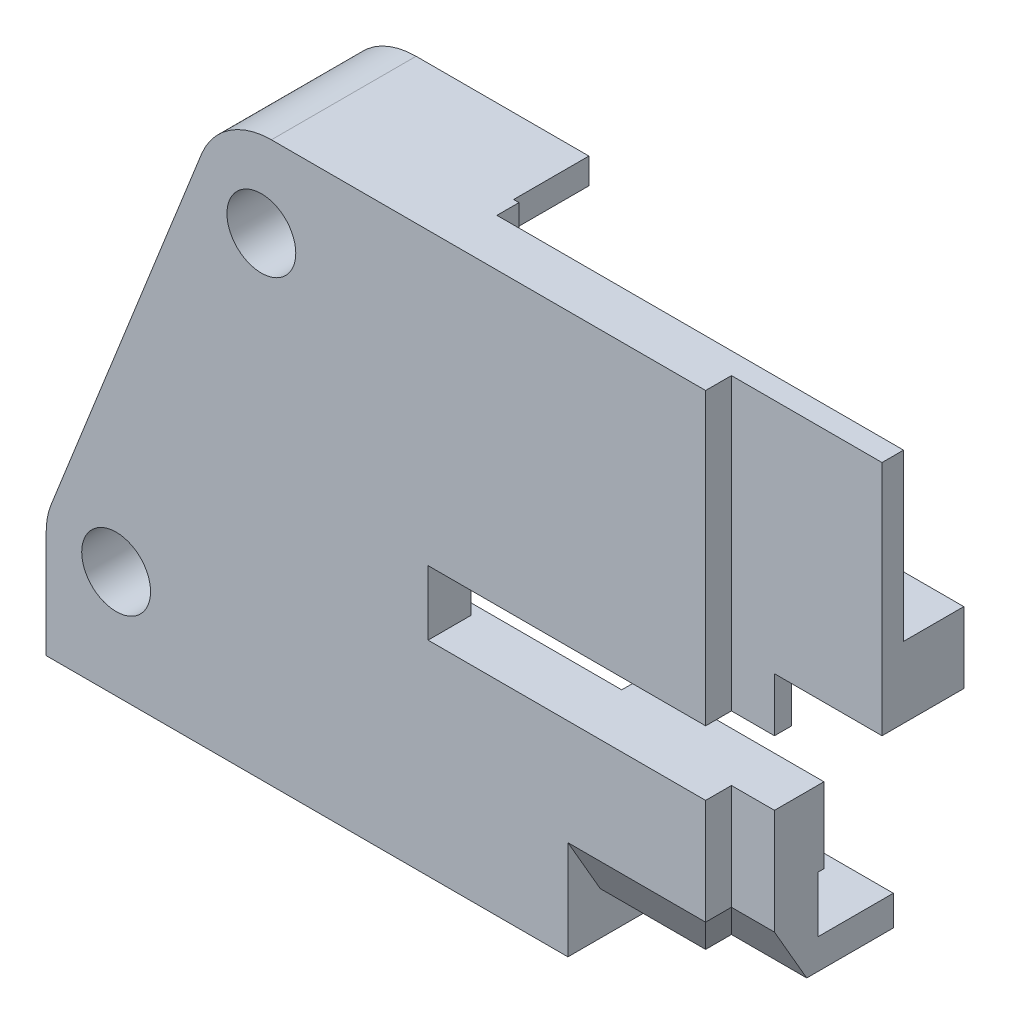
SolidWorks part; units mm, degrees
ref_plane "前视基准面" through (0, 0, 0) normal (0, 0, 1) x (1, 0, 0)
ref_plane "上视基准面" through (0, 0, 0) normal (0, 1, 0) x (1, 0, 0)
ref_plane "右视基准面" through (0, 0, 0) normal (1, 0, 0) x (0, 0, -1)
other "Configuration Table"
sketch "草图1" plane through (0, 0, 0) normal (0, 0, 1) x (1, 0, 0)
  line L1 (-4, 6.5) -> (6, 6.5)
  line L2 (-4, 6.5) -> (-4, -5)
  line L3 (-4, -5) -> (6, -5)
  line L4 (6, 6.5) -> (6, -5)
  circle A0 centre (0, 0) radius 1.6
  dimension "D1" = 3.2
  dimension "D2" = 5
  dimension "D3" = 4
  dimension "D4" = 11.5
  dimension "D5" = 10
extrude "凸台-拉伸1" add sketch "草图1" along normal blind 3
sketch "草图2" plane through (0, 0, 3) normal (0, 0, 1) x (1, 0, 0)
  line L1 (6, -5) -> (21, -5)
  line L2 (6, -5) -> (6, 1)
  line L3 (6, 1) -> (21, 1)
  line L4 (21, -5) -> (21, 1)
  dimension "D1" = 6
  dimension "D2" = 15
extrude "凸台-拉伸2" add sketch "草图2" against normal blind 5
fillet "圆角1" radius 1 1 edges at (-4, 0.75, 0)
sketch "草图3" plane through (0, 1, 0) normal (0, 1, 0) x (1, 0, 0)
  line L0 (21, -3) -> (6, -3) construction
  line L1 (6, 2) -> (11, 2)
  line L2 (6, 2) -> (6, -3)
  line L3 (6, -3) -> (11, -3)
  line L4 (11, 2) -> (11, -3)
  dimension "D1" = 5
extrude "凸台-拉伸3" add sketch "草图3" along normal blind 2
sketch "草图4" plane through (0, 3, 0) normal (0, 1, 0) x (1, 0, 0)
  line L0 (6, 2) -> (6, 0) construction
  line L1 (6, 0) -> (11, 0)
  line L2 (6, 0) -> (6, -3)
  line L3 (6, -3) -> (11, -3)
  line L4 (11, 0) -> (11, -3)
  dimension "D1" = 3
extrude "凸台-拉伸4" add sketch "草图4" along normal blind 19.5
sketch "草图5" plane through (0, 0, 0) normal (0, 0, -1) x (-1, 0, 0)
  line L0 (-6, 22.5) -> (-6, 6.5) construction
  line L1 (-6, 10) -> (-11, 10)
  line L2 (-6, 10) -> (-6, 13.5)
  line L3 (-6, 13.5) -> (-11, 13.5)
  line L4 (-11, 10) -> (-11, 13.5)
  line L5 (-11, 22.5) -> (-11, 3) construction
  line L6 (-11, 3) -> (-6, 3) construction
  line L7 (-11, 3) -> (-6, 3) construction
  dimension "D1" = 7
  dimension "D2" = 10.5
extrude "凸台-拉伸5" add sketch "草图5" along normal blind 3
sketch "草图6" plane through (6, 0, 0) normal (-1, 0, 0) x (0, 0, 1)
  line L1 (3, 22.5) -> (0, 22.5)
  line L2 (3, 22.5) -> (3, 14)
  line L3 (3, 14) -> (0, 14)
  line L4 (0, 22.5) -> (0, 14)
  line L5 (0, 22.5) -> (0, 13.5) construction
  dimension "D1" = 8.5
extrude "凸台-拉伸6" add sketch "草图6" along normal blind 3
sketch "草图7" plane through (0, 0, 0) normal (0, 0, -1) x (-1, 0, 0)
  line L6 (-11, 13.5) -> (-6, 13.5)
  line L7 (-6, 13.5) -> (-6, 14)
  line L8 (-6, 14) -> (-3, 14)
  line L9 (-3, 14) -> (-3, 22.5)
  line L10 (-3, 22.5) -> (-11, 22.5)
  line L11 (-11, 22.5) -> (-11, 13.5)
  line L12 (-11, 13.5) -> (-6, 13.5)
  line L13 (-6, 13.5) -> (-6, 14)
  line L14 (-6, 14) -> (-3, 14)
  line L15 (-3, 14) -> (-3, 22.5)
  line L16 (-3, 22.5) -> (-11, 22.5)
  line L17 (-11, 22.5) -> (-11, 13.5)
  dimension "D1" = 0
extrude "凸台-拉伸7" add sketch "草图7" along normal blind 1
sketch "草图8" plane through (0, 0, 3) normal (0, 0, 1) x (1, 0, 0)
  line L0 (21, 1) -> (11, 1) construction
  line L1 (11, 22.5) -> (14.5, 22.5)
  line L2 (11, 22.5) -> (11, 1)
  line L3 (11, 1) -> (14.5, 1)
  line L4 (14.5, 22.5) -> (14.5, 1)
  dimension "D1" = 3.5
extrude "凸台-拉伸8" add sketch "草图8" against normal blind 1
sketch "草图9" plane through (11, 0, 0) normal (1, 0, 0) x (0, 0, -1)
  line L0 (1, 22.5) -> (1, 13.5) construction
  line L1 (-2, 22.5) -> (1, 22.5)
  line L2 (-2, 22.5) -> (-2, 14.5)
  line L3 (-2, 14.5) -> (1, 14.5)
  line L4 (1, 22.5) -> (1, 14.5)
  dimension "D1" = 8
extrude "凸台-拉伸9" add sketch "草图9" along normal up to surface (3.5 mm away) up to face at (14.5, 11.75, 2.5)
sketch "草图10" plane through (11, 0, 0) normal (1, 0, 0) x (0, 0, -1)
  line L1 (-0.5, 4.5) -> (-3, 4.5)
  line L2 (-0.5, 4.5) -> (-0.5, 1)
  line L3 (-0.5, 1) -> (-3, 1)
  line L4 (-3, 4.5) -> (-3, 1)
  line L5 (-3, -5) -> (-3, 1) construction
  line L6 (2, 1) -> (-3, 1) construction
  line L7 (0, 10) -> (0, 3) construction
  dimension "D1" = 3.5
  dimension "D2" = 0.5
extrude "凸台-拉伸10" add sketch "草图10" along normal up to surface (10 mm away) up to face at (21, -2, 0.5)
sketch "草图11" plane through (11, 0, 0) normal (1, 0, 0) x (0, 0, -1)
  line L0 (-2, 14.5) -> (1, 14.5) construction
  line L1 (0, 14.5) -> (-3, 14.5)
  line L2 (0, 14.5) -> (0, 10.5)
  line L3 (0, 10.5) -> (-3, 10.5)
  line L4 (-3, 14.5) -> (-3, 10.5)
  line L5 (-3, 4.5) -> (-3, 22.5) construction
  dimension "D1" = 4
  dimension "D2" = 3
extrude "凸台-拉伸11" add sketch "草图11" along normal up to surface (10 mm away) up to face at (21, 0.1667, 0.5)
sketch "草图12" plane through (21, 0, 0) normal (1, 0, 0) x (0, 0, -1)
  line L1 (0, 14.5) -> (-1.5, 14.5)
  line L2 (0, 14.5) -> (0, 13.3)
  line L3 (0, 13.3) -> (-1.5, 13.3)
  line L4 (-1.5, 14.5) -> (-1.5, 13.3)
  dimension "D1" = 1.5
  dimension "D2" = 1.2
extrude "切除-拉伸1" cut sketch "草图12" against normal blind 2
sketch "草图13" plane through (14.5, 0, 0) normal (1, 0, 0) x (0, 0, -1)
  line L0 (-2, 10.5) -> (-2, 4.5) construction
  line L1 (-3, 10.5) -> (-2, 10.5)
  line L2 (-3, 10.5) -> (-3, 8)
  line L3 (-3, 8) -> (-2, 8)
  line L4 (-2, 10.5) -> (-2, 8)
  dimension "D1" = 2.5
extrude "凸台-拉伸12" add sketch "草图13" along normal up to surface (6.5 mm away) up to face at (21, 12.7667, 1.5)
sketch "草图14" plane through (14.5, 0, 0) normal (1, 0, 0) x (0, 0, -1)
  line L0 (1, 22.5) -> (-3, 22.5) construction
  line L1 (-1.8, 22.5) -> (-3, 22.5)
  line L2 (-1.8, 22.5) -> (-1.8, 14.5)
  line L3 (-1.8, 14.5) -> (-3, 14.5)
  line L4 (-3, 22.5) -> (-3, 14.5)
  dimension "D1" = 1.2
extrude "凸台-拉伸13" add sketch "草图14" along normal up to surface (6.5 mm away) up to face at (21, 11.575, 1.625)
sketch "草图15" plane through (0, 0, 1.8) normal (0, 0, -1) x (-1, 0, 0)
  line L1 (-14.5, 14.5) -> (-18.5, 14.5)
  line L2 (-14.5, 14.5) -> (-14.5, 18.5)
  line L3 (-14.5, 18.5) -> (-18.5, 18.5)
  line L4 (-18.5, 14.5) -> (-18.5, 18.5)
  dimension "D1" = 4
extrude "凸台-拉伸14" add sketch "草图15" along normal up to surface (2.8 mm away)
fillet "圆角2" radius 1 1 edges at (14.5, 18.5, 0.4)
sketch "草图16" plane through (0, 0, 3) normal (0, 0, 1) x (1, 0, 0)
  line L0 (3, 14) -> (3, 22.5) construction
  line L1 (3, 22.5) -> (21, 22.5) construction
  circle A0 centre (6.75, 17) radius 1.6
  dimension "D1" = 3.75
  dimension "D2" = 5.5
  dimension "D3" = 3.2
extrude "切除-拉伸2" cut sketch "草图16" against normal up to next
sketch "草图17" plane through (0, -5, 0) normal (0, -1, 0) x (1, 0, 0)
  line L1 (6, -2) -> (21, -2)
  line L2 (6, -2) -> (6, 3)
  line L3 (6, 3) -> (21, 3)
  line L4 (21, -2) -> (21, 3)
extrude "凸台-拉伸15" add sketch "草图17" along normal blind 2
sketch "草图18" plane through (21, 0, 0) normal (1, 0, 0) x (0, 0, -1)
  line L10 (0, 13.3) -> (-1.5, 13.3)
  line L11 (0, 13.3) -> (-1.5, 13.3)
  line L12 (-1.5, 14.5) -> (-1.8, 14.5)
  line L13 (-1.8, 14.5) -> (-1.8, 22.5)
  line L14 (-1.8, 22.5) -> (-3, 22.5)
  line L15 (-3, 22.5) -> (-3, 8)
  line L16 (-3, 8) -> (-2, 8)
  line L17 (-2, 8) -> (-2, 10.5)
  line L18 (-2, 10.5) -> (0, 10.5)
  line L19 (0, 10.5) -> (0, 13.3)
  line L22 (-1.5, 14.5) -> (-1.8, 14.5)
  line L23 (-1.8, 14.5) -> (-1.8, 22.5)
  line L24 (-1.8, 22.5) -> (-3, 22.5)
  line L25 (-3, 22.5) -> (-3, 8)
  line L26 (-3, 8) -> (-2, 8)
  line L27 (-2, 8) -> (-2, 10.5)
  line L28 (-2, 10.5) -> (0, 10.5)
  line L29 (0, 10.5) -> (0, 13.3)
  line L30 (-1.5, 13.3) -> (-1.5, 14.5)
  line L31 (-1.5, 13.3) -> (-1.5, 14.5)
  dimension "D1" = 0
extrude "凸台-拉伸16" add sketch "草图18" along normal blind 5.5
sketch "草图19" plane through (0, 0, 0) normal (0, 0, -1) x (-1, 0, 0)
  line L0 (-19, 13.3) -> (-26.5, 13.3) construction
  line L1 (-24.5, 13.3) -> (-26.5, 13.3)
  line L2 (-24.5, 13.3) -> (-24.5, 10.5)
  line L3 (-24.5, 10.5) -> (-26.5, 10.5)
  line L4 (-26.5, 13.3) -> (-26.5, 10.5)
  dimension "D1" = 2
extrude "凸台-拉伸17" add sketch "草图19" along normal blind 2
sketch "草图20" plane through (21, 0, 0) normal (1, 0, 0) x (0, 0, -1)
  line L1 (0.5, -3) -> (-3, -3)
  line L2 (0.5, 1) -> (0.5, 4.5)
  line L3 (0.5, 4.5) -> (-3, 4.5)
  line L4 (-3, -3) -> (-3, 4.5)
  line L5 (2, -7) -> (2, 1) construction
  line L7 (2, 1) -> (0.5, 1)
  line L8 (2, 1) -> (2, -3)
  line L9 (2, -3) -> (0.5, -3)
  dimension "D1" = 1.5
  dimension "D2" = 7.5
extrude "凸台-拉伸18" add sketch "草图20" along normal up to surface (5.5 mm away) up to face at (26.5, 13.76, 1.26)
sketch "草图21" plane through (26.5, 0, 0) normal (1, 0, 0) x (0, 0, -1)
  line L6 (-3, -3) -> (2, -3)
  line L7 (2, -3) -> (2, 1)
  line L8 (2, 1) -> (0.5, 1)
  line L9 (0.5, 1) -> (0.5, 4.5)
  line L10 (0.5, 4.5) -> (-3, 4.5)
  line L11 (-3, 4.5) -> (-3, -3)
  line L12 (-3, -3) -> (2, -3)
  line L13 (2, -3) -> (2, 1)
  line L14 (2, 1) -> (0.5, 1)
  line L15 (0.5, 1) -> (0.5, 4.5)
  line L16 (0.5, 4.5) -> (-3, 4.5)
  line L17 (-3, 4.5) -> (-3, -3)
  line L22 (-2, 10.5) -> (2, 10.5)
  line L23 (2, 10.5) -> (2, 13.3)
  line L24 (2, 13.3) -> (-1.5, 13.3)
  line L26 (-1.5, 14.5) -> (-1.8, 14.5)
  line L27 (-1.8, 14.5) -> (-1.8, 22.5)
  line L28 (-1.8, 22.5) -> (-3, 22.5)
  line L29 (-3, 22.5) -> (-3, 8)
  line L30 (-3, 8) -> (-2, 8)
  line L31 (-2, 8) -> (-2, 10.5)
  line L32 (-2, 10.5) -> (2, 10.5)
  line L33 (2, 10.5) -> (2, 13.3)
  line L36 (-1.5, 14.5) -> (-1.8, 14.5)
  line L37 (-1.8, 14.5) -> (-1.8, 22.5)
  line L38 (-1.8, 22.5) -> (-3, 22.5)
  line L39 (-3, 22.5) -> (-3, 8)
  line L40 (-3, 8) -> (-2, 8)
  line L41 (-2, 8) -> (-2, 10.5)
  line L42 (2, 13.3) -> (-1.5, 13.3)
  line L44 (-1.5, 13.3) -> (-1.5, 14.5)
  line L45 (-1.5, 13.3) -> (-1.5, 14.5)
  dimension "D1" = 0
  dimension "D2" = 0
extrude "凸台-拉伸19" add sketch "草图21" along normal blind 2.9
sketch "草图22" plane through (0, 0, 2) normal (0, 0, -1) x (-1, 0, 0)
  line L6 (-11, 10.5) -> (-29.4, 10.5)
  line L7 (-29.4, 10.5) -> (-29.4, 8)
  line L8 (-29.4, 8) -> (-14.5, 8)
  line L9 (-14.5, 8) -> (-14.5, 4.5)
  line L10 (-14.5, 4.5) -> (-11, 4.5)
  line L11 (-11, 4.5) -> (-11, 10.5)
  line L12 (-11, 10.5) -> (-29.4, 10.5)
  line L13 (-29.4, 10.5) -> (-29.4, 8)
  line L14 (-29.4, 8) -> (-14.5, 8)
  line L15 (-14.5, 8) -> (-14.5, 4.5)
  line L16 (-14.5, 4.5) -> (-11, 4.5)
  line L17 (-11, 4.5) -> (-11, 10.5)
  dimension "D1" = 0
extrude "凸台-拉伸20" add sketch "草图22" along normal blind 0.5
sketch "草图23" plane through (0, 8, 0) normal (0, -1, 0) x (1, 0, 0)
  line L4 (14.5, 3) -> (14.5, 1.5)
  line L5 (14.5, 1.5) -> (29.4, 1.5)
  line L6 (29.4, 1.5) -> (29.4, 3)
  line L7 (29.4, 3) -> (14.5, 3)
  line L8 (14.5, 3) -> (14.5, 1.5)
  line L9 (14.5, 1.5) -> (29.4, 1.5)
  line L10 (29.4, 1.5) -> (29.4, 3)
  line L11 (29.4, 3) -> (14.5, 3)
  dimension "D1" = 0
extrude "凸台-拉伸21" add sketch "草图23" along normal blind 0.5
sketch "草图24" plane through (29.4, 0, 0) normal (1, 0, 0) x (0, 0, -1)
  line L0 (-1.5, 10.5) -> (0, 10.5) construction
  line L1 (2, 13.3) -> (-1, 13.3)
  line L2 (2, 13.3) -> (2, 10.5)
  line L3 (2, 10.5) -> (-1, 10.5)
  line L4 (-1, 13.3) -> (-1, 10.5)
  dimension "D1" = 3
extrude "凸台-拉伸22" add sketch "草图24" along normal blind 5
sketch "草图25" plane through (0, 22.5, 0) normal (0, 1, 0) x (1, 0, 0)
  line L0 (9.9, 1) -> (9.9, -3)
  line L6 (14.5, -1.8) -> (14.5, 1)
  line L7 (14.5, 1) -> (3, 1)
  line L8 (3, 1) -> (3, -3)
  line L9 (3, -3) -> (29.4, -3)
  line L10 (29.4, -3) -> (29.4, -1.8)
  line L11 (29.4, -1.8) -> (14.5, -1.8)
  line L12 (14.5, -1.8) -> (14.5, 1)
  line L13 (14.5, 1) -> (9.9, 1)
  line L15 (9.9, -3) -> (29.4, -3)
  line L16 (29.4, -3) -> (29.4, -1.8)
  line L17 (29.4, -1.8) -> (14.5, -1.8)
  dimension "D2" = 19.5
  dimension "D1" = 0
extrude "凸台-拉伸23" add sketch "草图25" along normal blind 3.2
sketch "草图26" plane through (0, 13.3, 0) normal (0, 1, 0) x (1, 0, 0)
  line L0 (29.4, -1.8) -> (18.5, -1.8) construction
  line L1 (18.5, 0) -> (28.5, 0)
  line L2 (18.5, 0) -> (18.5, -1.8)
  line L3 (18.5, -1.8) -> (28.5, -1.8)
  line L4 (28.5, 0) -> (28.5, -1.8)
  dimension "D1" = 10
extrude "凸台-拉伸24" add sketch "草图26" along normal blind 3
sketch "草图27" plane through (0, 0, 0) normal (0, 0, -1) x (-1, 0, 0)
  line L1 (-28.5, 16.3) -> (-18.5, 16.3)
  line L2 (-28.5, 16.3) -> (-28.5, 14.5)
  line L3 (-28.5, 14.5) -> (-18.5, 14.5)
  line L4 (-18.5, 16.3) -> (-18.5, 14.5)
extrude "凸台-拉伸25" add sketch "草图27" along normal up to surface (1 mm away)
sketch "草图28" plane through (0, 0, -1) normal (0, 0, -1) x (-1, 0, 0)
  line L0 (-3, 14) -> (-3, 22.5) construction
  line L1 (-14.5, 25.7) -> (-3, 25.7)
  line L2 (-14.5, 25.7) -> (-14.5, 13.5)
  line L3 (-14.5, 13.5) -> (-3, 13.5)
  line L4 (-3, 25.7) -> (-3, 13.5)
  line L5 (-11, 13.5) -> (-6, 13.5) construction
extrude "切除-拉伸3" cut sketch "草图28" against normal offset from surface (0.775 mm away) 3.225 up to face at (8.35, 17, 3)
sketch "草图29" plane through (6, 0, 0) normal (-1, 0, 0) x (0, 0, 1)
  line L8 (3, 14) -> (-0.225, 14)
  line L9 (-0.225, 14) -> (-0.225, 13.5)
  line L10 (-0.225, 13.5) -> (-3, 13.5)
  line L11 (-3, 13.5) -> (-3, 10)
  line L12 (-3, 10) -> (0, 10)
  line L13 (0, 10) -> (0, 6.5)
  line L14 (0, 6.5) -> (3, 6.5)
  line L15 (3, 6.5) -> (3, 14)
  line L16 (3, 14) -> (-0.225, 14)
  line L17 (-0.225, 14) -> (-0.225, 13.5)
  line L18 (-0.225, 13.5) -> (-3, 13.5)
  line L19 (-3, 13.5) -> (-3, 10)
  line L20 (-3, 10) -> (0, 10)
  line L21 (0, 10) -> (0, 6.5)
  line L22 (0, 6.5) -> (3, 6.5)
  line L23 (3, 6.5) -> (3, 14)
  dimension "D1" = 0
extrude "切除-拉伸4" cut sketch "草图29" against normal blind 0.5
sketch "草图30" plane through (6.5, 0, 0) normal (-1, 0, 0) x (0, 0, 1)
  line L1 (0, 6.5) -> (3, 6.5)
  line L2 (0, 6.5) -> (0, 14)
  line L3 (0, 14) -> (3, 14)
  line L4 (3, 6.5) -> (3, 14)
extrude "凸台-拉伸26" add sketch "草图30" along normal up to surface (3.5 mm away) up to face at (3, 18.25, 1.3875)
sketch "草图31" plane through (0, 0, 0) normal (0, 0, -1) x (-1, 0, 0)
  line L10 (3, 6.5) -> (-3, 6.5)
  line L11 (-3, 6.5) -> (-3, 14)
  line L12 (-3, 14) -> (-6.5, 14)
  line L13 (-6.5, 14) -> (-6.5, 10)
  line L14 (-6.5, 10) -> (-11, 10)
  line L15 (-11, 10) -> (-11, 3)
  line L16 (-11, 3) -> (-6, 3)
  line L17 (-6, 3) -> (-6, -5)
  line L18 (-6, -5) -> (3, -5)
  line L19 (3, -5) -> (3, 6.5)
  line L20 (3, 6.5) -> (-3, 6.5)
  line L21 (-3, 6.5) -> (-3, 14)
  line L22 (-3, 14) -> (-6.5, 14)
  line L23 (-6.5, 14) -> (-6.5, 10)
  line L24 (-6.5, 10) -> (-11, 10)
  line L25 (-11, 10) -> (-11, 3)
  line L26 (-11, 3) -> (-6, 3)
  line L27 (-6, 3) -> (-6, -5)
  line L28 (-6, -5) -> (3, -5)
  line L29 (3, -5) -> (3, 6.5)
  circle A0 centre (0, 0) radius 1.6 construction
  circle A1 centre (0, 0) radius 1.6
  dimension "D1" = 0
extrude "凸台-拉伸27" add sketch "草图31" along normal blind 0.225
sketch "草图32" plane through (0, 0, -2) normal (0, 0, -1) x (-1, 0, 0)
  line L8 (-6, -7) -> (-6, 3)
  line L9 (-6, 3) -> (-11, 3)
  line L10 (-11, 3) -> (-11, 1)
  line L11 (-11, 1) -> (-29.4, 1)
  line L12 (-29.4, 1) -> (-29.4, -3)
  line L13 (-29.4, -3) -> (-21, -3)
  line L14 (-21, -3) -> (-21, -7)
  line L15 (-21, -7) -> (-6, -7)
  line L16 (-6, -7) -> (-6, 3)
  line L17 (-6, 3) -> (-11, 3)
  line L18 (-11, 3) -> (-11, 1)
  line L19 (-11, 1) -> (-29.4, 1)
  line L20 (-29.4, 1) -> (-29.4, -3)
  line L21 (-29.4, -3) -> (-21, -3)
  line L22 (-21, -3) -> (-21, -7)
  line L23 (-21, -7) -> (-6, -7)
  dimension "D1" = 0
extrude "切除-拉伸5" cut sketch "草图32" against normal up to surface (1.775 mm away)
sketch "草图33" plane through (0, 0, 1.8) normal (0, 0, -1) x (-1, 0, 0)
  line L1 (-18.5, 16.3) -> (-14.5, 16.3)
  line L2 (-18.5, 16.3) -> (-18.5, 19.5)
  line L3 (-18.5, 19.5) -> (-14.5, 19.5)
  line L4 (-14.5, 16.3) -> (-14.5, 19.5)
extrude "切除-拉伸6" cut sketch "草图33" along normal up to surface (2.8 mm away) up to face at (19.7561, 16.8418, -1)
sketch "草图34" plane through (14.5, 0, 0) normal (1, 0, 0) x (0, 0, -1)
  line L4 (0.225, 16.3) -> (0.225, 25.7)
  line L5 (0.225, 25.7) -> (-1.8, 25.7)
  line L6 (-1.8, 25.7) -> (-1.8, 16.3)
  line L7 (-1.8, 16.3) -> (0.225, 16.3)
  line L8 (0.225, 16.3) -> (0.225, 25.7)
  line L9 (0.225, 25.7) -> (-1.8, 25.7)
  line L10 (-1.8, 25.7) -> (-1.8, 16.3)
  line L11 (-1.8, 16.3) -> (0.225, 16.3)
  dimension "D1" = 0
extrude "凸台-拉伸28" add sketch "草图34" along normal blind 2
sketch "草图35" plane through (14.5, 0, 0) normal (-1, 0, 0) x (0, 0, 1)
  line L8 (-0.225, 16.3) -> (-1, 16.3)
  line L9 (-1, 16.3) -> (-1, 14.5)
  line L10 (-1, 14.5) -> (-0.225, 14.5)
  line L11 (-0.225, 14.5) -> (-0.225, 16.3)
  line L12 (-0.225, 16.3) -> (-1, 16.3)
  line L13 (-1, 16.3) -> (-1, 14.5)
  line L14 (-1, 14.5) -> (-0.225, 14.5)
  line L15 (-0.225, 14.5) -> (-0.225, 16.3)
  dimension "D1" = 0
extrude "切除-拉伸7" cut sketch "草图35" against normal up to surface (2 mm away) up to face at (16.5, 21, 0.7875)
sketch "草图36" plane through (0, 0, -0.225) normal (0, 0, -1) x (-1, 0, 0)
  line L1 (-29.4, 25.7) -> (-9.9, 25.7)
  line L2 (-29.4, 25.7) -> (-29.4, 22.5)
  line L3 (-29.4, 22.5) -> (-9.9, 22.5)
  line L4 (-9.9, 25.7) -> (-9.9, 22.5)
extrude "切除-拉伸8" cut sketch "草图36" against normal up to next
sketch "草图37" plane through (6, 0, 0) normal (-1, 0, 0) x (0, 0, 1)
  line L4 (-0.225, -5) -> (-0.225, -7)
  line L5 (-0.225, -7) -> (3, -7)
  line L6 (3, -7) -> (3, -5)
  line L7 (3, -5) -> (-0.225, -5)
  line L8 (-0.225, -5) -> (-0.225, -7)
  line L9 (-0.225, -7) -> (3, -7)
  line L10 (3, -7) -> (3, -5)
  line L11 (3, -5) -> (-0.225, -5)
  dimension "D1" = 0
extrude "切除-拉伸9" cut sketch "草图37" against normal up to next
sketch "草图39" plane through (0, 0, 3) normal (0, 0, 1) x (1, 0, 0)
  line L0 (29.4, 22.5) -> (29.4, 7.5) construction
  line L1 (3, 22.5) -> (29.4, 22.5)
  line L2 (3, 22.5) -> (3, 21)
  line L3 (3, 21) -> (29.4, 21)
  line L4 (29.4, 22.5) -> (29.4, 21)
  circle A0 centre (6.75, 17) radius 1.6 construction
  dimension "D1" = 4
extrude "切除-拉伸10" cut sketch "草图39" against normal up to next
sketch "草图40" plane through (0, 6.5, 0) normal (0, 1, 0) x (1, 0, 0)
  line L1 (-3, 0.225) -> (-4, 0.225)
  line L2 (-3, 0.225) -> (-3, -3)
  line L3 (-3, -3) -> (-4, -3)
  line L4 (-4, 0.225) -> (-4, -3)
extrude "凸台-拉伸29" add sketch "草图40" against normal up to surface (11.5 mm away) up to face at (4.6321, -5, 1.0571)
sketch "草图41" plane through (34.4, 0, 0) normal (1, 0, 0) x (0, 0, -1)
  line L1 (-1.8, 21) -> (-0.8, 21)
  line L2 (-1.8, 21) -> (-1.8, 10.5)
  line L3 (-1.8, 10.5) -> (-0.8, 10.5)
  line L4 (-0.8, 21) -> (-0.8, 10.5)
  line L6 (-1.5, 10.5) -> (0, 10.5) construction
  dimension "D1" = 1
extrude "凸台-拉伸30" add sketch "草图41" against normal up to next
sketch "草图42" plane through (29.4, 0, 0) normal (1, 0, 0) x (0, 0, -1)
  line L0 (-0.5, 4.5) -> (-1.5, 4.5) construction
  line L1 (0.225, -3) -> (-0.775, -3)
  line L2 (0.225, -3) -> (0.225, 4.5)
  line L3 (0.225, 4.5) -> (-0.775, 4.5)
  line L4 (-0.775, -3) -> (-0.775, 4.5)
  line L5 (0.5, 4.5) -> (-3, 4.5) construction
  dimension "D1" = 1
extrude "凸台-拉伸31" add sketch "草图42" along normal blind 3
sketch "草图43" plane through (0, 21, 0) normal (0, 1, 0) x (1, 0, 0)
  line L0 (16.5, 0.225) -> (3, 0.225) construction
  line L1 (11, 0.225) -> (3, 0.225)
  line L2 (11, 0.225) -> (11, -3)
  line L3 (11, -3) -> (3, -3)
  line L4 (3, 0.225) -> (3, -3)
  dimension "D1" = 8
extrude "凸台-拉伸32" add sketch "草图43" along normal blind 1
sketch "草图44" plane through (0, 0, 0.775) normal (0, 0, 1) x (1, 0, 0)
  line L4 (29.4, 4.5) -> (29.4, -3)
  line L5 (29.4, -3) -> (32.4, -3)
  line L6 (32.4, -3) -> (32.4, 4.5)
  line L7 (32.4, 4.5) -> (29.4, 4.5)
  line L8 (29.4, 4.5) -> (29.4, -3)
  line L9 (29.4, -3) -> (32.4, -3)
  line L10 (32.4, -3) -> (32.4, 4.5)
  line L11 (32.4, 4.5) -> (29.4, 4.5)
  dimension "D1" = 0
extrude "切除-拉伸11" cut sketch "草图44" against normal up to next
fillet "圆角3" radius 5 1 edges at (3, 22, 1.3875)
sketch "草图45" plane through (0, 0, 0) normal (0, 0, -1) x (-1, 0, 0)
  line L6 (-11, 14.5) -> (-28.5, 14.5)
  line L7 (-28.5, 14.5) -> (-28.5, 13.3)
  line L8 (-28.5, 13.3) -> (-24.5, 13.3)
  line L9 (-24.5, 13.3) -> (-24.5, 10.5)
  line L10 (-24.5, 10.5) -> (-11, 10.5)
  line L11 (-11, 10.5) -> (-11, 14.5)
  line L12 (-11, 14.5) -> (-28.5, 14.5)
  line L13 (-28.5, 14.5) -> (-28.5, 13.3)
  line L14 (-28.5, 13.3) -> (-24.5, 13.3)
  line L15 (-24.5, 13.3) -> (-24.5, 10.5)
  line L16 (-24.5, 10.5) -> (-11, 10.5)
  line L17 (-11, 10.5) -> (-11, 14.5)
  dimension "D1" = 0
extrude "凸台-拉伸33" add sketch "草图45" along normal blind 1.2
sketch "草图46" plane through (0, 10.5, 0) normal (0, -1, 0) x (1, 0, 0)
  line L8 (11, 1.5) -> (11, -1.2)
  line L9 (11, -1.2) -> (24.5, -1.2)
  line L10 (24.5, -1.2) -> (24.5, -2)
  line L11 (24.5, -2) -> (34.4, -2)
  line L12 (34.4, -2) -> (34.4, 1.8)
  line L13 (34.4, 1.8) -> (29.4, 1.8)
  line L14 (29.4, 1.8) -> (29.4, 1.5)
  line L15 (29.4, 1.5) -> (11, 1.5)
  line L16 (11, 1.5) -> (11, -1.2)
  line L17 (11, -1.2) -> (24.5, -1.2)
  line L18 (24.5, -1.2) -> (24.5, -2)
  line L19 (24.5, -2) -> (34.4, -2)
  line L20 (34.4, -2) -> (34.4, 1.8)
  line L21 (34.4, 1.8) -> (29.4, 1.8)
  line L22 (29.4, 1.8) -> (29.4, 1.5)
  line L23 (29.4, 1.5) -> (11, 1.5)
  dimension "D1" = 0
extrude "凸台-拉伸34" add sketch "草图46" along normal blind 0.5
sketch "草图47" plane through (0, 0, 1.5) normal (0, 0, -1) x (-1, 0, 0)
  line L6 (-11, 10) -> (-29.4, 10)
  line L7 (-29.4, 10) -> (-29.4, 7.5)
  line L8 (-29.4, 7.5) -> (-14.5, 7.5)
  line L9 (-14.5, 7.5) -> (-14.5, 4.5)
  line L10 (-14.5, 4.5) -> (-11, 4.5)
  line L11 (-11, 4.5) -> (-11, 10)
  line L12 (-11, 10) -> (-29.4, 10)
  line L13 (-29.4, 10) -> (-29.4, 7.5)
  line L14 (-29.4, 7.5) -> (-14.5, 7.5)
  line L15 (-14.5, 7.5) -> (-14.5, 4.5)
  line L16 (-14.5, 4.5) -> (-11, 4.5)
  line L17 (-11, 4.5) -> (-11, 10)
  dimension "D1" = 0
extrude "凸台-拉伸35" add sketch "草图47" along normal blind 0.5
sketch "草图48" plane through (0, 0, -0.225) normal (0, 0, -1) x (-1, 0, 0)
  line L0 (-8, 22) -> (4, 22)
  line L1 (4, 22) -> (4, 6.5)
  line L2 (4, 6.5) -> (-3, 6.5)
  line L3 (-3, 6.5) -> (-3, 17)
  arc A0 (-3, 17) -> (-8, 22) centre (-8, 17) ccw construction
  arc A1 (-3, 17) -> (-8, 22) centre (-8, 17) ccw
extrude "凸台-拉伸36" add sketch "草图48" against normal up to surface (3.225 mm away) up to face at (14.371, 8.3357, 3)
sketch "草图49" plane through (0, 0, -0.225) normal (0, 0, -1) x (-1, 0, 0)
  line L1 (-11, 21) -> (4, 21)
  line L2 (-11, 21) -> (-11, 22)
  line L3 (-11, 22) -> (4, 22)
  line L4 (4, 21) -> (4, 22)
  line L5 (-11, 21) -> (4, 22) construction
  line L6 (-11, 22) -> (4, 21) construction
  point P4 (-3.5, 21.5)
extrude "切除-拉伸12" cut sketch "草图49" against normal up to next
sketch "草图50" plane through (0, 0, -0.225) normal (0, 0, -1) x (-1, 0, 0)
  circle A0 centre (-6.75, 17) radius 3.25
  circle A1 centre (0, 0) radius 3.25
  circle A2 centre (0, 0) radius 1.6 construction
  circle A3 centre (-6.75, 17) radius 1.6 construction
  circle A4 centre (0, 0) radius 1.6
  circle A5 centre (-6.75, 17) radius 1.6
  dimension "D1" = 6.5
extrude "凸台-拉伸38" add sketch "草图50" along normal blind 3.5
sketch "草图51" plane through (16.5, 0, 0) normal (1, 0, 0) x (0, 0, -1)
  line L4 (-0.8, 21) -> (-0.8, 16.3)
  line L5 (-0.8, 16.3) -> (0.225, 16.3)
  line L6 (0.225, 16.3) -> (0.225, 21)
  line L7 (0.225, 21) -> (-0.8, 21)
  line L8 (-0.8, 21) -> (-0.8, 16.3)
  line L9 (-0.8, 16.3) -> (0.225, 16.3)
  line L10 (0.225, 16.3) -> (0.225, 21)
  line L11 (0.225, 21) -> (-0.8, 21)
  dimension "D1" = 0
extrude "切除-拉伸13" cut sketch "草图51" against normal blind 1
sketch "草图52" plane through (0, -5, 0) normal (0, -1, 0) x (1, 0, 0)
  line L0 (21, -0.225) -> (-4, -0.225) construction
  line L1 (-4, 3) -> (-4, -0.225) construction
  circle A0 centre (8.25, -2.725) radius 4
  dimension "D1" = 2.5
  dimension "D2" = 8
  dimension "D3" = 12.25
extrude "切除-拉伸14" cut sketch "草图52" against normal blind 10
sketch "草图53" plane through (0, 0, -0.225) normal (0, 0, -1) x (-1, 0, 0)
  line L1 (-15.25, 21) -> (-15.25, 19.8)
  line L2 (-15.5, 21) -> (-34.4, 21) construction
  line L7 (-15.25, 21) -> (4, 21)
  line L8 (4, 21) -> (4, -5)
  line L9 (2.8, 19.8) -> (2.8, -5)
  line L10 (-15.5, 19.8) -> (2.8, 19.8)
  line L11 (2.8, 19.8) -> (2.8, -5)
  line L12 (-15.25, 19.8) -> (2.8, 19.8)
  line L13 (4, -5) -> (2.8, -5)
  line L16 (-29.4, -1.6) -> (-29.4, -3)
  line L17 (-29.4, -3) -> (-21, -3)
  line L18 (-29.4, -1.6) -> (-19.6, -1.6)
  line L19 (-19.6, -1.6) -> (-19.6, -5)
  line L20 (-29.4, -1.6) -> (-19.6, -1.6)
  line L21 (-19.6, -1.6) -> (-19.6, -5)
  line L22 (-21, -3) -> (-21, -5)
  line L23 (-21, -5) -> (-19.6, -5)
  circle A0 centre (-6.75, 17) radius 3.25 construction
  dimension "D1" = 8.5
  dimension "D2" = 1.4
  dimension "D3" = 1.2
extrude "凸台-拉伸39" add sketch "草图53" along normal up to surface (3.5 mm away) up to face at (3.5, 17, -3.725)
sketch "草图54" plane through (0, -5, 0) normal (0, -1, 0) x (1, 0, 0)
  line L0 (11.3725, -0.225) -> (19.6, -0.225)
  line L1 (-2.8, -0.225) -> (5.1275, -0.225)
  line L2 (-2.8, -0.225) -> (-2.8, -3.725)
  line L3 (-2.8, -3.725) -> (4.377, -3.725)
  line L4 (19.6, -0.225) -> (19.6, -3.725)
  line L5 (-2.8, -0.225) -> (19.6, -3.725) construction
  line L6 (-2.8, -3.725) -> (19.6, -0.225) construction
  line L7 (12.123, -3.725) -> (19.6, -3.725)
  arc A0 (5.1275, -0.225) -> (4.377, -3.725) centre (8.25, -2.725) ccw
  arc A1 (11.3725, -0.225) -> (5.1275, -0.225) centre (8.25, -2.725) ccw construction
  arc A2 (12.123, -3.725) -> (11.3725, -0.225) centre (8.25, -2.725) ccw
  point P4 (8.4, -1.975)
extrude "凸台-拉伸40" add sketch "草图54" against normal blind 1.2
sketch "草图55" plane through (0, 0, -0.225) normal (0, 0, -1) x (-1, 0, 0)
  line L2 (-19.6, -3.8) -> (-11.3725, -3.8)
  line L3 (-19.6, -3.8) -> (-11.3725, -3.8)
  line L11 (-11.3725, -3.8) -> (-11.3725, 1)
  line L12 (-11.3725, -3.8) -> (-11.3725, 1)
  line L13 (-11.3725, 1) -> (-21, 1)
  line L14 (-11.3725, 1) -> (-21, 1)
  line L15 (-21, 1) -> (-29.4, 1)
  line L16 (-21, 1) -> (-29.4, 1)
  line L17 (-29.4, 1) -> (-29.4, -1.6)
  line L18 (-29.4, 1) -> (-29.4, -1.6)
  line L19 (-29.4, -1.6) -> (-19.6, -1.6)
  line L20 (-29.4, -1.6) -> (-19.6, -1.6)
  line L21 (-19.6, -1.6) -> (-19.6, -3.8)
  line L22 (-19.6, -1.6) -> (-19.6, -3.8)
  dimension "D1" = 0
sketch "草图56" plane through (0, 0, -0.225) normal (0, 0, -1) x (-1, 0, 0)
  line L0 (-3.7294, 18.1994) -> (3.0206, 1.1994)
  line L1 (-3.7294, 18.1994) -> (-4.8414, 21)
  line L2 (4, 21) -> (-15.25, 21) construction
  line L3 (3.25, 0) -> (3.25, -5)
  line L4 (-4.377, -5) -> (4, -5) construction
  line L5 (3.25, -5) -> (4, -5)
  line L6 (4, -5) -> (4, 21)
  line L7 (4, 21) -> (-4.8414, 21)
  arc A0 (-8.4, 19.8) -> (-5.1, 19.8) centre (-6.75, 17) ccw construction
  arc A1 (2.8, 1.65) -> (2.8, -1.65) centre (0, 0) ccw construction
  arc A2 (3.25, 0) -> (3.0206, 1.1994) centre (0, 0) ccw
extrude "切除-拉伸15" cut sketch "草图56" against normal through all both and the other way through all
fillet "圆角5" radius 3.5 1 edges at (4.8414, 21, -0.3625)
sketch "草图57" plane through (0, 0, -0.225) normal (0, 0, -1) x (-1, 0, 0)
  line L9 (-3.7294, 18.1994) -> (-3.9646, 18.7916)
  line L10 (-4.5793, 19.8) -> (-5.1, 19.8)
  line L11 (-3.7294, 18.1994) -> (-3.9646, 18.7916)
  line L12 (-4.5793, 19.8) -> (-5.1, 19.8)
  arc A7 (-3.9646, 18.7916) -> (-4.5793, 19.8) centre (-7.2175, 17.5) ccw
  arc A8 (-3.7294, 18.1994) -> (-5.1, 19.8) centre (-6.75, 17) ccw
  arc A9 (-3.9646, 18.7916) -> (-4.5793, 19.8) centre (-7.2175, 17.5) ccw
  arc A10 (-3.7294, 18.1994) -> (-5.1, 19.8) centre (-6.75, 17) ccw
  dimension "D1" = 0
extrude "凸台-拉伸42" add sketch "草图57" along normal up to surface (3.5 mm away) up to face at (9.2778, 19.2393, -3.725)
sketch "草图58" plane through (0, 0, -0.225) normal (0, 0, -1) x (-1, 0, 0)
  line L1 (2.8, 1.7549) -> (-3.7294, 18.1994) construction
  line L2 (1.4988, 1.2383) -> (-5.0306, 17.6827)
  line L3 (0.7333, 3.1662) -> (-4.0445, 15.1992)
  line L4 (2.8, 1.7549) -> (-3.7294, 18.1994)
  line L5 (2.8, 1.7549) -> (2.8, 1.65) construction
  line L6 (2.8, 1.7549) -> (2.8, 1.65)
  arc A0 (-8.4, 19.8) -> (-3.7294, 18.1994) centre (-6.75, 17) ccw construction
  arc A1 (-4.0445, 15.1992) -> (-3.7294, 18.1994) centre (-6.75, 17) ccw
  arc A2 (2.8, 1.65) -> (2.8, -1.65) centre (0, 0) ccw construction
  arc A3 (2.8, 1.65) -> (0.7333, 3.1662) centre (0, 0) ccw
  dimension "D1" = 1.4
extrude "凸台-拉伸43" add sketch "草图58" along normal up to surface (3.5 mm away) up to face at (9.2018, 19.0028, -3.725)
fillet "圆角6" radius 1 4 edges at (-2.8, -1.65, -1.975) (-0.7333, 3.1662, -1.975) (8.4, 19.8, -1.975) (4.0445, 15.1992, -1.975)
sketch "草图59" plane through (0, 0, 3) normal (0, 0, 1) x (1, 0, 0)
  line L1 (29.4, 21) -> (27.4, 21)
  line L2 (29.4, 21) -> (29.4, -3)
  line L3 (29.4, -3) -> (27.4, -3)
  line L4 (27.4, 21) -> (27.4, -3)
  line L5 (29.4, 21) -> (27.4, -3) construction
  line L6 (29.4, -3) -> (27.4, 21) construction
  point P4 (28.4, 9)
  point P6 (29.4, -3)
  dimension "D1" = 2
extrude "切除-拉伸16" cut sketch "草图59" against normal up to surface (1.2 mm away) up to face at (31.9, 15.5, 1.8)
chamfer "倒角1" distance 1.5 angle 60 3 edges at (24.2, -3, 3) (27.4, -3, 2.4) (28.4, -3, 1.8) first distance on face at (25.9333, -3, 0.3583)
equation "\"。5\"=10"
